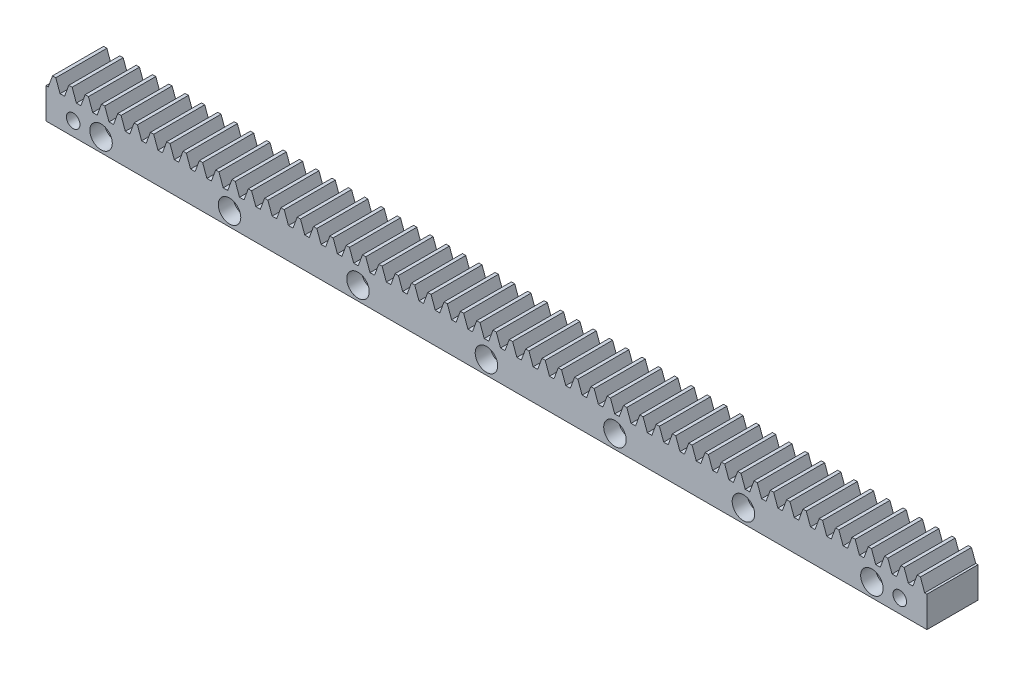
SolidWorks part; units mm, degrees
extrude "Blank" add sketch "BlankSke" against normal blind 59
sketch "BlankSke" plane through (0, 0, 0) normal (0, 0, 1) x (1, 0, 0)
  line L1 (0, 0) -> (1017.88, 0)
  line L2 (0, 0) -> (0, 49)
  line L3 (0, 49) -> (1017.88, 49)
  line L4 (1017.88, 0) -> (1017.88, 49)
  dimension "Length" = 1017.88
ref_plane "Plane1" through (0, 0, 0) normal (0, 0, 1) x (1, 0, 0)
ref_plane "Plane2" through (0, 0, 0) normal (0, 1, 0) x (1, 0, 0)
ref_plane "Plane3" through (0, 0, 0) normal (1, 0, 0) x (0, 0, -1)
sketch "HoldingSke" plane through (0, 0, 0) normal (0, 1, 0) x (1, 0, 0)
  line L0 (0, 0) -> (0.0232, 0.165)
  line L1 (-15, 0) -> (100, 0) construction
  line L2 (0, 0) -> (-2.1039, 2.3779)
  line L3 (0, 0) -> (-11.863, 4.5341)
  line L4 (0, 0) -> (4.8292, 7.1596)
  line L5 (0, 0) -> (-23.7986, -8.8762)
  line L6 (0, 0) -> (-10.5278, -7.1032)
  line L9 (-71.009, 38.7566) -> (885.4854, 386.8921)
  line L10 (-76.2, 8.3779) -> (-33.2, 8.3779)
  line L11 (0, 0) -> (-59, 0)
  line L12 (-76.2, 101.6) -> (-75.993, 101.6)
  line L13 (24.9733, 27.94) -> (52.9518, 28.4284)
  line L14 (24.9733, 27.94) -> (24.9743, 27.94)
  line L15 (24.9733, 27.94) -> (100.4006, 29.5858)
  circle A0 centre (0, 0) radius 19.05
  circle A1 centre (0, 0) radius 21.5
  circle A2 centre (0, 0) radius 12.7
  dimension "Num_teeth" = 56
  dimension "Width" = 59
  dimension "Length" = 1017.88
  dimension "Pitch_height" = 43
sketch "TooCutSkeIll" plane through (0, 0, 0) normal (0, 0, 1) x (1, 0, 0)
  line L0 (-7.4597, 48.8421) -> (-2.9631, 36.4876)
  line L1 (-1.5526, 35.5) -> (1.5526, 35.5)
  line L2 (2.9631, 36.4876) -> (7.4597, 48.8421)
  line L3 (1017.88, 49) -> (0, 49) construction
  line L4 (0, 0) -> (0, 64.897) construction
  line L5 (-13.208, 43) -> (12.954, 43) construction
  line L6 (0, 0) -> (1017.88, 0) construction
  line L7 (5.3334, 43) -> (5.3334, 48.7463) construction
  line L8 (-5.3334, 43) -> (-5.3334, 48.7463) construction
  line L9 (7.6853, 49) -> (7.6853, 49.0254)
  line L10 (-7.6853, 49) -> (-7.6853, 49.0254)
  line L11 (-7.6853, 49.0254) -> (7.6853, 49.0254)
  arc A0 (1.5526, 35.5) -> (2.9631, 36.4876) centre (1.5526, 37.001) ccw
  arc A1 (-2.9631, 36.4876) -> (-1.5526, 35.5) centre (-1.5526, 37.001) ccw
  arc A2 (7.6853, 49) -> (7.4597, 48.8421) centre (7.6853, 48.76) ccw
  arc A3 (-7.4597, 48.8421) -> (-7.6853, 49) centre (-7.6853, 48.76) ccw
  dimension "Addendum_plus" = 6.0254
  dimension "Pitch_height" = 43
  dimension "Pressure_angle" = 20
  dimension "Gap_width" = 10.6668
  dimension "Dedendum" = 7.5
extrude "ToothCutIll" [suppressed] cut sketch "TooCutSkeIll" against normal through all
sketch "TooCutSkeSim" plane through (0, 0, 0) normal (0, 0, 1) x (1, 0, 0)
  line L0 (2.6036, 35.5) -> (-2.6036, 35.5)
  line L1 (7.5265, 49.0254) -> (2.6036, 35.5)
  line L2 (0, 17.4625) -> (0, 53.467) construction
  line L3 (7.5265, 49.0254) -> (-7.5265, 49.0254)
  line L6 (-7.5265, 49.0254) -> (-2.6036, 35.5)
  line L9 (-5.3334, 43) -> (5.3334, 43) construction
  line L10 (0, 0) -> (1017.88, 0) construction
  line L11 (5.3334, 43) -> (5.3334, 53.467) construction
  line L12 (-5.3334, 43) -> (-5.3334, 53.467) construction
  dimension "Addendum_plus" = 6.0254
  dimension "Pitch_height" = 43
  dimension "Pressure_angle" = 20
  dimension "Gap_width" = 10.6668
  dimension "Dedendum" = 7.5
extrude "ToothCutSim" cut sketch "TooCutSkeSim" against normal through all
pattern_linear "TeethCuts" count 56 spacing 18.8496 along (1, 0, 0) of "ToothCutIll", "ToothCutSim"
sketch "Sketch2" plane through (0, 0, 0) normal (0, 0, 1) x (1, 0, 0)
  line L0 (0, 35.5) -> (0, 0) construction
  line L1 (0, 0) -> (1017.88, 0) construction
  line L2 (1017.88, 0) -> (1017.88, 35.5) construction
  circle A0 centre (31.4, 16) radius 7.85
  circle A1 centre (986.48, 16) radius 7.85
  dimension "D1" = 15.7
  dimension "D5" = 15.7
  dimension "D2" = 31.4
  dimension "D3" = 16
  dimension "D4" = 16
  dimension "D6" = 31.4
extrude "Cut-Extrude1" cut sketch "Sketch2" against normal blind 202
sketch "Sketch3" plane through (0, 0, 0) normal (0, 0, 1) x (1, 0, 0)
  line L0 (0, 35.5) -> (0, 0) construction
  circle A0 centre (63.6, 16) radius 9
  dimension "D1" = 18
  dimension "D2" = 63.6
extrude "Cut-Extrude2" cut sketch "Sketch3" against normal blind 202
sketch "Sketch4" plane through (0, 0, 0) normal (0, 0, 1) x (1, 0, 0)
  circle A0 centre (63.6, 16) radius 13
  dimension "D1" = 26
extrude "Cut-Extrude3" cut sketch "Sketch4" against normal blind 17
sketch "Sketch5" plane through (0, 0, 0) normal (0, 0, 1) x (1, 0, 0)
  line L0 (63.6, 16) -> (31.4, 16)
  line L1 (986.48, 16) -> (954.28, 16)
  point P5 (0, 0)
  point P6 (0, 0)
  dimension "D1" = 32.2
  dimension "D2" = 32.2
pattern_linear "LPattern1" count 2 spacing 890.68 along (1, 0, 0) of "Cut-Extrude2", "Cut-Extrude3"
pattern_linear "LPattern2" count 6 spacing 148.4467 along (1, 0, 0) of "Cut-Extrude2", "Cut-Extrude3"
equation "' \"Module@HoldingSke\" = 6.35"
equation "' \"Num_teeth@HoldingSke\" = 12"
equation "' \"Ap@HoldingSke\" =  20"
equation "' \"Ap@HoldingSke\" = 20"
equation "' \"Width@HoldingSke\" = 0.25 * 25.4"
equation "' \"Show_teeth@HoldingSke\" = 500"
equation "' \"Backlash@HoldingSke\" = 0.009 * 25.4"
equation "' \"Addendum_fac@HoldingSke\" = 1.0"
equation "' \"Dedendum_fac@HoldingSke\" = 1.25"
equation "' \"Dedendum_add@HoldingSke\" = 0.00005 * 25.4"
equation "' \"Clearance_fac@HoldingSke\" = 0.25"
equation "' \"Pitch_height@HoldingSke\" = 1 * 25.4"
equation "' \"Length@HoldingSke\" = 4.71 * 25.4"
equation "\"Pitch@HoldingSke\" = 1 / \"Module@HoldingSke\""
equation "\"MPH@HoldingSke\" = \"Dedendum_fac@HoldingSke\" / \"Pitch@HoldingSke\" + 2 * \"Dedendum_add@HoldingSke\" + 0.002 * 25.4"
equation "\"MPH@HoldingSke\" = ((sgn( \"MPH@HoldingSke\" - \"Pitch_height@HoldingSke\")+1)*( \"MPH@HoldingSke\" - \"Pitch_height@HoldingSke\"))/2 + \"Pitch_height@HoldingSke\""
equation "\"Blank_height@BlankSke\" = \"Pitch_height@HoldingSke\" + \"Addendum_fac@HoldingSke\"  / \"Pitch@HoldingSke\" "
equation "\"Length@BlankSke\" =  \"Length@HoldingSke\""
equation "\"Face_width@Blank\" = \"Width@HoldingSke\""
equation "\"Pressure_angle@TooCutSkeIll\" = \"Ap@HoldingSke\""
equation "\"Addendum_plus@TooCutSkeIll\" =  \"Addendum_fac@HoldingSke\"  / \"Pitch@HoldingSke\" + 0.001 *25.4"
equation "\"Dedendum@TooCutSkeIll\" = \"Dedendum_fac@HoldingSke\"  / \"Pitch@HoldingSke\""
equation "\"Pitch_height@TooCutSkeIll\" =  \"MPH@HoldingSke\""
equation "\"Gap_width@TooCutSkeIll\" = 3.14159265 / 2 / \"Pitch@HoldingSke\" + 6 * \"Backlash@HoldingSke\""
equation "\"Pressure_angle@TooCutSkeSim\" = \"Ap@HoldingSke\""
equation "\"Addendum_plus@TooCutSkeSim\" =  \"Addendum_fac@HoldingSke\"  / \"Pitch@HoldingSke\" + 0.001 * 25.4"
equation "\"Dedendum@TooCutSkeSim\" = \"Dedendum_fac@HoldingSke\"  / \"Pitch@HoldingSke\""
equation "\"Pitch_height@TooCutSkeSim\" =  \"MPH@HoldingSke\""
equation "\"Gap_width@TooCutSkeSim\" = 3.14159265 / 2 / \"Pitch@HoldingSke\" + 6 * \"Backlash@HoldingSke\""
equation "\"Root_fillet@TooCutSkeIll\" = \"Clearance_fac@HoldingSke\" / \"Pitch@HoldingSke\" + \"Dedendum_add@HoldingSke\""
equation "\"Break_rad@TooCutSkeIll\" = 0.02 / \"Pitch@HoldingSke\" * 2"
equation "\"Linear_pitch@TeethCuts\" = 3.14159265 / \"Pitch@HoldingSke\""
equation "\"Num_teeth@HoldingSke\" = int( ( \"Length@HoldingSke\" + 0 ) / (3.14159265 / \"Pitch@HoldingSke\")) + 0.9999  + 1"
equation " \"Num_teeth@TeethCuts\" = int( \"Show_teeth@HoldingSke\" ) + 1"
equation " \"Num_teeth@TeethCuts\" = ((sgn( \"Num_teeth@TeethCuts\" - \"Num_teeth@HoldingSke\" )-1)*( \"Num_teeth@TeethCuts\" - \"Num_teeth@HoldingSke\" ))/-2+ \"Num_teeth@HoldingSke\""
equation " \"Num_teeth@TeethCuts\" = ((sgn( \"Num_teeth@TeethCuts\" - 2.0)+1)*( \"Num_teeth@TeethCuts\" - 2.0))/2 +2.0"
